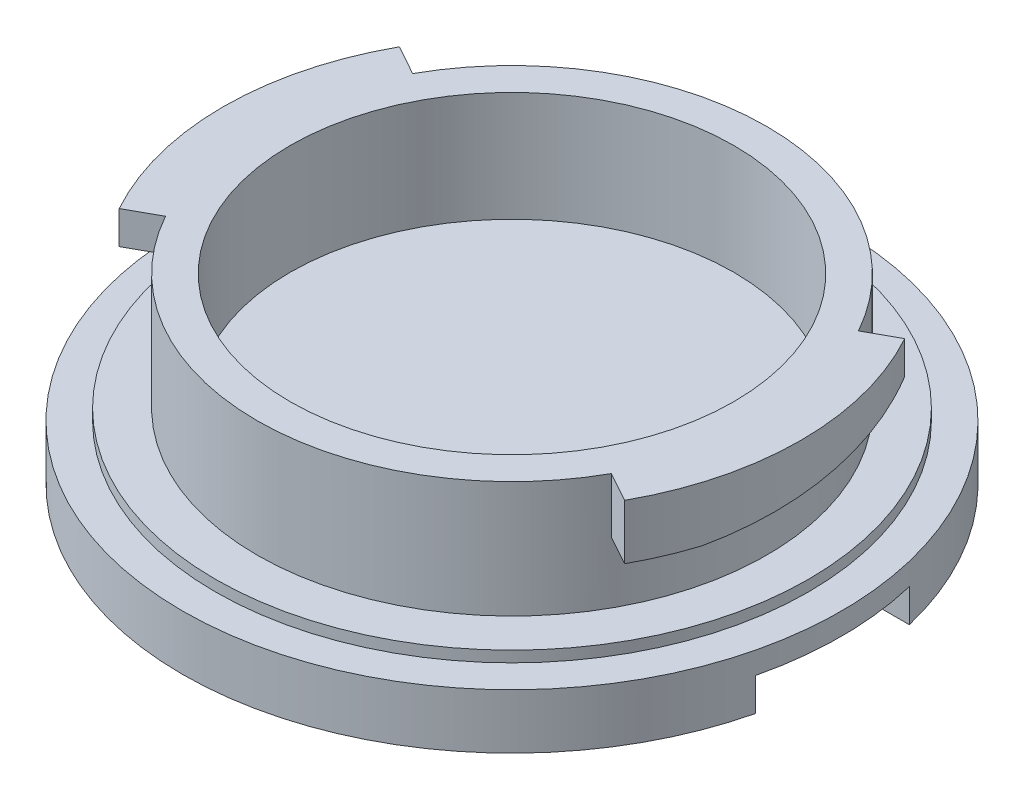
SolidWorks part; units mm, degrees
ref_plane "Front Plane" through (0, 0, 0) normal (0, 0, 1) x (1, 0, 0)
ref_plane "Top Plane" through (0, 0, 0) normal (0, 1, 0) x (1, 0, 0)
ref_plane "Right Plane" through (0, 0, 0) normal (1, 0, 0) x (0, 0, -1)
sketch "Sketch1" plane through (0, 0, 0) normal (0, 1, 0) x (1, 0, 0)
  circle A0 centre (0, 0) radius 15
extrude "Boss-Extrude1" add sketch "Sketch1" along normal blind 2.5
sketch "Sketch2" plane through (0, 2.5, 0) normal (0, 1, 0) x (1, 0, 0)
  circle A0 centre (0, 0) radius 13.5
extrude "Boss-Extrude2" add sketch "Sketch2" along normal blind 0.5
sketch "Sketch3" plane through (0, 3, 0) normal (0, 1, 0) x (1, 0, 0)
  circle A0 centre (0, 0) radius 11.6
extrude "Boss-Extrude3" add sketch "Sketch3" along normal blind 5.3
sketch "Sketch4" plane through (0, 8.3, 0) normal (0, 1, 0) x (1, 0, 0)
  circle A0 centre (0, 0) radius 10.1
extrude "Cut-Extrude1" cut sketch "Sketch4" against normal blind 5
sketch "Sketch6" plane through (0, 0, 0) normal (0, -1, 0) x (1, 0, 0)
  line L1 (-11.0896, 2) -> (11.0896, 2)
  line L2 (-11.0896, 2) -> (-11.0896, -2)
  line L3 (-11.0896, -2) -> (11.0896, -2)
  line L4 (11.0896, 2) -> (11.0896, -2)
  line L5 (-11.0896, 2) -> (11.0896, -2) construction
  line L6 (-11.0896, -2) -> (11.0896, 2) construction
  circle A0 centre (0, 0) radius 10
extrude "Cut-Extrude2" cut sketch "Sketch6" against normal blind 2 contours L1 A0 | L3 A0 region at (0, 0, 5.3437) region at (0, 0, -5.3437)
sketch "Sketch7" plane through (0, 8.3, 0) normal (0, 1, 0) x (1, 0, 0)
  line L0 (0, 0) -> (11.5012, -6.3752)
  line L1 (0, 0) -> (11.5012, 6.3752)
  line L2 (0, 0) -> (-11.5012, -6.3752)
  line L3 (0, 0) -> (-11.5012, 6.3752)
  circle A0 centre (0, 0) radius 13.15
  circle M6 centre (0, 0) radius 11.6
extrude "Boss-Extrude4" add sketch "Sketch7" against normal blind 2.5 contours L0 A0 L1 M6 | L3 A0 L2 M6 region at (11.8688, 8.3, 0) region at (-11.8688, 8.3, 0)
sketch "Sketch8" plane through (0, 0, 0) normal (0, -1, 0) x (1, 0, 0)
  line L0 (0, 2) -> (0, -2)
  line L1 (13, -3.5) -> (17.2352, -3.5)
  line L2 (13, -3.5) -> (13, 3.5)
  line L3 (13, 3.5) -> (17.2352, 3.5)
  line L4 (17.2352, -3.5) -> (17.2352, 3.5)
  line L5 (-9.798, 2) -> (9.798, 2) construction
  line L6 (-9.798, -2) -> (9.798, -2) construction
  line L7 (-13, 3.5) -> (-17.2352, 3.5)
  line L8 (-13, -3.5) -> (-13, 3.5)
  line L9 (-13, -3.5) -> (-17.2352, -3.5)
  line L10 (-17.2352, -3.5) -> (-17.2352, 3.5)
  circle M8 centre (0, 0) radius 15
extrude "Cut-Extrude3" cut sketch "Sketch8" against normal blind 1.5 contours L3 L2 L1 M8 | L9 L8 L7 M8 region at (13.9355, 0, 0) region at (-13.9355, 0, 0)
chamfer "Chamfer1" distance 1.5 angle 45 2 edges at (13, 1.5, 0) (-13, 1.5, 0)
chamfer "Chamfer3" distance 1 angle 84 2 edges at (-10.8234, 5.8, 5.9995) (10.8234, 5.8, -5.9995) first distance on face at (-10.8234, 7.05, 5.9995) first distance on face at (10.8234, 7.05, -5.9995)
